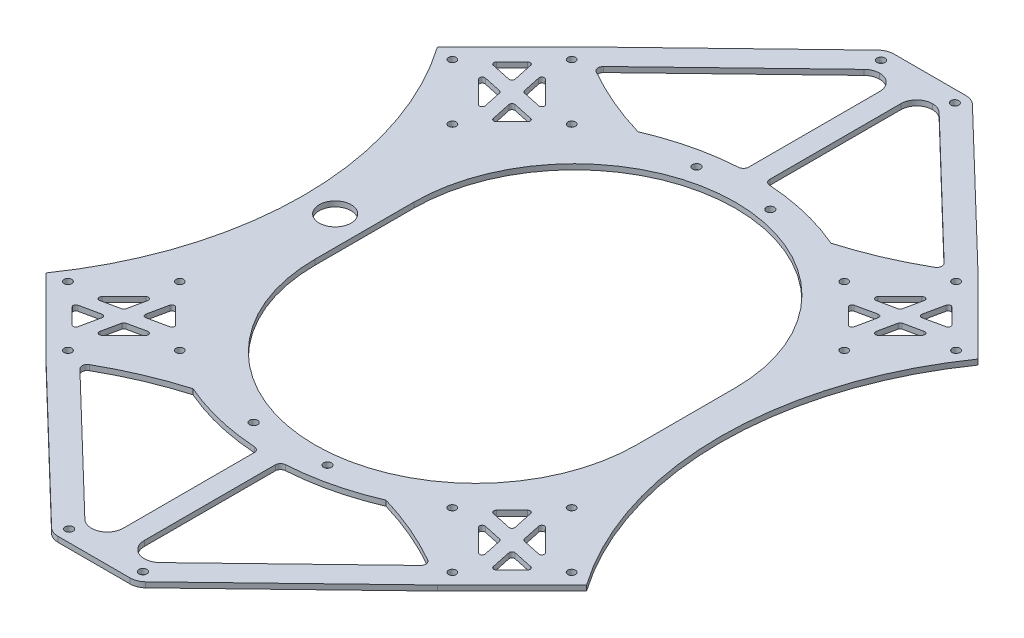
SolidWorks part; units mm, degrees
material "Thornel Mat VMA"
ref_plane "前视基准面" through (0, 0, 0) normal (0, 0, 1) x (1, 0, 0)
ref_plane "上视基准面" through (0, 0, 0) normal (0, 1, 0) x (1, 0, 0)
ref_plane "右视基准面" through (0, 0, 0) normal (1, 0, 0) x (0, 0, -1)
sketch "草图1" plane through (0, 0, 0) normal (0, 1, 0) x (1, 0, 0)
  line L0 (-74.2462, 102.5305) -> (-102.5305, 74.2462)
  line L1 (74.2462, 102.5305) -> (-74.2462, 102.5305)
  line L2 (102.5305, 74.2462) -> (102.5305, -74.2462)
  line L3 (74.2462, -102.5305) -> (-74.2462, -102.5305)
  line L4 (-102.5305, 74.2462) -> (-102.5305, -74.2462)
  line L5 (102.5305, 102.5305) -> (-102.5305, -102.5305) construction
  line L6 (102.5305, -102.5305) -> (-102.5305, 102.5305) construction
  line L7 (102.5305, -74.2462) -> (74.2462, -102.5305)
  line L8 (-102.5305, -74.2462) -> (-74.2462, -102.5305)
  line L9 (74.2462, 102.5305) -> (102.5305, 74.2462)
  line L10 (-102.5305, 102.5305) -> (-102.5305, -102.5305) construction
  line L11 (-102.5305, -102.5305) -> (102.5305, -102.5305) construction
  line L12 (102.5305, -102.5305) -> (102.5305, 102.5305) construction
  line L13 (102.5305, 102.5305) -> (-102.5305, 102.5305) construction
  point P0 (0, 0)
  dimension "D1" = 250
  dimension "D2" = 40
extrude "凸台-拉伸1" add sketch "草图1" along normal blind 2
hole_wizard "孔1" positions "草图4" profile "草图5" legacy
sketch "草图4" plane through (0, 2, 0) normal (0, 1, 0) x (1, 0, 0)
  point P0 (-95.5397, 72.9159)
  point P3 (-74.3265, 51.7027)
  point P6 (-51.6991, 74.3301)
  point P9 (-72.9123, 95.5433)
  point P16 (72.9159, 95.5397)
  point P17 (51.7027, 74.3265)
  point P18 (74.3301, 51.6991)
  point P19 (95.5433, 72.9123)
  point P20 (95.5397, -72.9159)
  point P21 (74.3265, -51.7027)
  point P22 (51.6991, -74.3301)
  point P23 (72.9123, -95.5433)
  point P24 (-72.9159, -95.5397)
  point P25 (-51.7027, -74.3265)
  point P26 (-74.3301, -51.6991)
  point P27 (-95.5433, -72.9123)
  dimension "D1" = 4
sketch "草图5" plane through (-95.5397, 2, -72.9159) normal (1, 0, 0) x (0, 0, 1)
  line L0 (0, 0) -> (0, 100)
  line L1 (0, 100) -> (1.45, 100)
  line L2 (1.45, 100) -> (1.45, 0)
  line L3 (1.45, 0) -> (0, 0)
  line L4 (0, 110) -> (0, -10) construction
  dimension "直径" = 2.9
  dimension "深度" = 100
sketch "草图7" plane through (0, 2, 0) normal (0, 1, 0) x (1, 0, 0)
  line L0 (-95.5397, 72.9159) -> (-51.6991, 74.3301) construction
  line L1 (-86.393, 80.4842) -> (-80.4806, 86.3966)
  line L2 (-84.1601, 71.4358) -> (-75.8066, 63.0823)
  line L3 (-71.4322, 84.1637) -> (-63.0787, 75.8102)
  line L4 (-66.7582, 60.8494) -> (-60.8458, 66.7618)
  line L5 (-89.8008, 77.0764) -> (-57.438, 70.1696) construction
  line L6 (-77.0728, 89.8044) -> (-70.166, 57.4416) construction
  line L7 (-49.2242, 67.6126) -> (-79.6109, 97.9993) construction
  line L8 (-74.2462, 102.5305) -> (-102.5305, 74.2462) construction
  line L9 (-85.8946, 78.7991) -> (-78.378, 77.1949)
  line L10 (-83.2443, 73.1208) -> (-76.36, 71.6516)
  line L11 (-87.6941, 79.1831) -> (-89.8008, 77.0764) construction
  line L12 (-89.8008, 77.0764) -> (-86.5509, 73.8265) construction
  line L13 (-60.6879, 73.4195) -> (-57.438, 70.1696) construction
  line L14 (-57.438, 70.1696) -> (-59.5447, 68.0629) construction
  line L15 (-67.4604, 74.8648) -> (-68.504, 69.975) construction
  line L16 (-73.6194, 73.623) -> (-67.2554, 79.987) construction
  line L17 (-74.1216, 63.9981) -> (-75.5908, 70.8824)
  line L18 (-68.4433, 61.3478) -> (-70.0475, 68.8644)
  line L19 (-70.8788, 75.5944) -> (-63.9945, 74.1252)
  line L20 (-77.1913, 78.3816) -> (-78.7955, 85.8982)
  line L21 (-68.8608, 70.0511) -> (-61.3442, 68.4469)
  line L22 (-71.648, 76.3636) -> (-73.1172, 83.2479)
  line L23 (80.4842, 86.393) -> (86.3966, 80.4806)
  line L24 (71.4358, 84.1601) -> (63.0823, 75.8066)
  line L25 (84.1637, 71.4322) -> (75.8102, 63.0787)
  line L26 (60.8494, 66.7582) -> (66.7618, 60.8458)
  line L27 (78.7991, 85.8946) -> (77.1949, 78.378)
  line L28 (73.1208, 83.2443) -> (71.6516, 76.36)
  line L29 (63.9981, 74.1216) -> (70.8824, 75.5908)
  line L30 (61.3478, 68.4433) -> (68.8644, 70.0475)
  line L31 (75.5944, 70.8788) -> (74.1252, 63.9945)
  line L32 (78.3816, 77.1913) -> (85.8982, 78.7955)
  line L33 (70.0511, 68.8608) -> (68.4469, 61.3442)
  line L34 (76.3636, 71.648) -> (83.2479, 73.1172)
  line L35 (72.9159, 95.5397) -> (74.3301, 51.6991) construction
  line L36 (77.0764, 89.8008) -> (70.1696, 57.438) construction
  line L37 (89.8044, 77.0728) -> (57.4416, 70.166) construction
  line L38 (79.1831, 87.6941) -> (77.0764, 89.8008) construction
  line L39 (77.0764, 89.8008) -> (73.8265, 86.5509) construction
  line L40 (73.4195, 60.6879) -> (70.1696, 57.438) construction
  line L41 (70.1696, 57.438) -> (68.0629, 59.5447) construction
  line L42 (74.8648, 67.4604) -> (69.975, 68.504) construction
  line L43 (73.623, 73.6194) -> (79.987, 67.2554) construction
  line L44 (86.393, -80.4842) -> (80.4806, -86.3966)
  line L45 (84.1601, -71.4358) -> (75.8066, -63.0823)
  line L46 (71.4322, -84.1637) -> (63.0787, -75.8102)
  line L47 (66.7582, -60.8494) -> (60.8458, -66.7618)
  line L48 (85.8946, -78.7991) -> (78.378, -77.1949)
  line L49 (83.2443, -73.1208) -> (76.36, -71.6516)
  line L50 (74.1216, -63.9981) -> (75.5908, -70.8824)
  line L51 (68.4433, -61.3478) -> (70.0475, -68.8644)
  line L52 (70.8788, -75.5944) -> (63.9945, -74.1252)
  line L53 (77.1913, -78.3816) -> (78.7955, -85.8982)
  line L54 (68.8608, -70.0511) -> (61.3442, -68.4469)
  line L55 (71.648, -76.3636) -> (73.1172, -83.2479)
  line L56 (95.5397, -72.9159) -> (51.6991, -74.3301) construction
  line L57 (89.8008, -77.0764) -> (57.438, -70.1696) construction
  line L58 (77.0728, -89.8044) -> (70.166, -57.4416) construction
  line L59 (87.6941, -79.1831) -> (89.8008, -77.0764) construction
  line L60 (89.8008, -77.0764) -> (86.5509, -73.8265) construction
  line L61 (60.6879, -73.4195) -> (57.438, -70.1696) construction
  line L62 (57.438, -70.1696) -> (59.5447, -68.0629) construction
  line L63 (67.4604, -74.8648) -> (68.504, -69.975) construction
  line L64 (73.6194, -73.623) -> (67.2554, -79.987) construction
  line L65 (-80.4842, -86.393) -> (-86.3966, -80.4806)
  line L66 (-71.4358, -84.1601) -> (-63.0823, -75.8066)
  line L67 (-84.1637, -71.4322) -> (-75.8102, -63.0787)
  line L68 (-60.8494, -66.7582) -> (-66.7618, -60.8458)
  line L69 (-78.7991, -85.8946) -> (-77.1949, -78.378)
  line L70 (-73.1208, -83.2443) -> (-71.6516, -76.36)
  line L71 (-63.9981, -74.1216) -> (-70.8824, -75.5908)
  line L72 (-61.3478, -68.4433) -> (-68.8644, -70.0475)
  line L73 (-75.5944, -70.8788) -> (-74.1252, -63.9945)
  line L74 (-78.3816, -77.1913) -> (-85.8982, -78.7955)
  line L75 (-70.0511, -68.8608) -> (-68.4469, -61.3442)
  line L76 (-76.3636, -71.648) -> (-83.2479, -73.1172)
  line L77 (-72.9159, -95.5397) -> (-74.3301, -51.6991) construction
  line L78 (-77.0764, -89.8008) -> (-70.1696, -57.438) construction
  line L79 (-89.8044, -77.0728) -> (-57.4416, -70.166) construction
  line L80 (-79.1831, -87.6941) -> (-77.0764, -89.8008) construction
  line L81 (-77.0764, -89.8008) -> (-73.8265, -86.5509) construction
  line L82 (-73.4195, -60.6879) -> (-70.1696, -57.438) construction
  line L83 (-70.1696, -57.438) -> (-68.0629, -59.5447) construction
  line L84 (-74.8648, -67.4604) -> (-69.975, -68.504) construction
  line L85 (-73.623, -73.6194) -> (-79.987, -67.2554) construction
  arc A0 (-63.0787, 75.8102) -> (-63.9945, 74.1252) centre (-63.7858, 75.1031) cw
  arc A1 (-70.8788, 75.5944) -> (-71.648, 76.3636) centre (-70.67, 76.5724) cw
  arc A2 (-71.4322, 84.1637) -> (-73.1172, 83.2479) centre (-72.1393, 83.4566) ccw
  arc A3 (-78.7955, 85.8982) -> (-80.4806, 86.3966) centre (-79.7735, 85.6895) ccw
  arc A4 (-85.8946, 78.7991) -> (-86.393, 80.4842) centre (-85.6859, 79.7771) cw
  arc A5 (-78.378, 77.1949) -> (-77.1913, 78.3816) centre (-78.1693, 78.1729) ccw
  arc A6 (-66.7582, 60.8494) -> (-68.4433, 61.3478) centre (-67.4653, 61.5565) cw
  arc A7 (-60.8458, 66.7618) -> (-61.3442, 68.4469) centre (-61.5529, 67.4689) ccw
  arc A8 (-68.8608, 70.0511) -> (-70.0475, 68.8644) centre (-69.0695, 69.0731) ccw
  arc A9 (-75.8066, 63.0823) -> (-74.1216, 63.9981) centre (-75.0995, 63.7894) ccw
  arc A10 (-75.5908, 70.8824) -> (-76.36, 71.6516) centre (-76.5688, 70.6736) ccw
  arc A11 (-83.2443, 73.1208) -> (-84.1601, 71.4358) centre (-83.453, 72.1429) ccw
  arc A12 (75.8102, 63.0787) -> (74.1252, 63.9945) centre (75.1031, 63.7858) cw
  arc A13 (75.5944, 70.8788) -> (76.3636, 71.648) centre (76.5724, 70.67) cw
  arc A14 (84.1637, 71.4322) -> (83.2479, 73.1172) centre (83.4566, 72.1393) ccw
  arc A15 (85.8982, 78.7955) -> (86.3966, 80.4806) centre (85.6895, 79.7735) ccw
  arc A16 (78.7991, 85.8946) -> (80.4842, 86.393) centre (79.7771, 85.6859) cw
  arc A17 (77.1949, 78.378) -> (78.3816, 77.1913) centre (78.1729, 78.1693) ccw
  arc A18 (60.8494, 66.7582) -> (61.3478, 68.4433) centre (61.5565, 67.4653) cw
  arc A19 (66.7618, 60.8458) -> (68.4469, 61.3442) centre (67.4689, 61.5529) ccw
  arc A20 (70.0511, 68.8608) -> (68.8644, 70.0475) centre (69.0731, 69.0695) ccw
  arc A21 (63.0823, 75.8066) -> (63.9981, 74.1216) centre (63.7894, 75.0995) ccw
  arc A22 (70.8824, 75.5908) -> (71.6516, 76.36) centre (70.6736, 76.5688) ccw
  arc A23 (73.1208, 83.2443) -> (71.4358, 84.1601) centre (72.1429, 83.453) ccw
  arc A24 (63.0787, -75.8102) -> (63.9945, -74.1252) centre (63.7858, -75.1031) cw
  arc A25 (70.8788, -75.5944) -> (71.648, -76.3636) centre (70.67, -76.5724) cw
  arc A26 (71.4322, -84.1637) -> (73.1172, -83.2479) centre (72.1393, -83.4566) ccw
  arc A27 (78.7955, -85.8982) -> (80.4806, -86.3966) centre (79.7735, -85.6895) ccw
  arc A28 (85.8946, -78.7991) -> (86.393, -80.4842) centre (85.6859, -79.7771) cw
  arc A29 (78.378, -77.1949) -> (77.1913, -78.3816) centre (78.1693, -78.1729) ccw
  arc A30 (66.7582, -60.8494) -> (68.4433, -61.3478) centre (67.4653, -61.5565) cw
  arc A31 (60.8458, -66.7618) -> (61.3442, -68.4469) centre (61.5529, -67.4689) ccw
  arc A32 (68.8608, -70.0511) -> (70.0475, -68.8644) centre (69.0695, -69.0731) ccw
  arc A33 (75.8066, -63.0823) -> (74.1216, -63.9981) centre (75.0995, -63.7894) ccw
  arc A34 (75.5908, -70.8824) -> (76.36, -71.6516) centre (76.5688, -70.6736) ccw
  arc A35 (83.2443, -73.1208) -> (84.1601, -71.4358) centre (83.453, -72.1429) ccw
  arc A36 (-75.8102, -63.0787) -> (-74.1252, -63.9945) centre (-75.1031, -63.7858) cw
  arc A37 (-75.5944, -70.8788) -> (-76.3636, -71.648) centre (-76.5724, -70.67) cw
  arc A38 (-84.1637, -71.4322) -> (-83.2479, -73.1172) centre (-83.4566, -72.1393) ccw
  arc A39 (-85.8982, -78.7955) -> (-86.3966, -80.4806) centre (-85.6895, -79.7735) ccw
  arc A40 (-78.7991, -85.8946) -> (-80.4842, -86.393) centre (-79.7771, -85.6859) cw
  arc A41 (-77.1949, -78.378) -> (-78.3816, -77.1913) centre (-78.1729, -78.1693) ccw
  arc A42 (-60.8494, -66.7582) -> (-61.3478, -68.4433) centre (-61.5565, -67.4653) cw
  arc A43 (-66.7618, -60.8458) -> (-68.4469, -61.3442) centre (-67.4689, -61.5529) ccw
  arc A44 (-70.0511, -68.8608) -> (-68.8644, -70.0475) centre (-69.0731, -69.0695) ccw
  arc A45 (-63.0823, -75.8066) -> (-63.9981, -74.1216) centre (-63.7894, -75.0995) ccw
  arc A46 (-70.8824, -75.5908) -> (-71.6516, -76.36) centre (-70.6736, -76.5688) ccw
  arc A47 (-73.1208, -83.2443) -> (-71.4358, -84.1601) centre (-72.1429, -83.453) ccw
  point P5 (-73.6194, 73.623)
  point P14 (-72.9123, 95.5433)
  point P21 (-67.9822, 72.4199)
  point P38 (-71.5127, 75.7297)
  point P41 (-73.8229, 86.5545)
  point P44 (-79.1795, 87.6977)
  point P50 (-76.8693, 76.8729)
  point P53 (-68.0593, 59.5483)
  point P59 (-70.3695, 70.3731)
  point P62 (-73.4159, 60.6915)
  point P73 (73.623, 73.6194)
  point P84 (72.4199, 67.9822)
  point P126 (73.6194, -73.623)
  point P137 (67.9822, -72.4199)
  point P179 (-73.623, -73.6194)
  point P190 (-72.4199, -67.9822)
  point P230 (0, 0)
  dimension "D4" = 1
  dimension "D1" = 7
  dimension "D2" = 7
  dimension "D3" = 5
  dimension "D5" = 4
extrude "切除-拉伸2" cut sketch "草图7" against normal through all both and the other way through all
sketch "草图8" plane through (0, 2, 0) normal (0, 1, 0) x (1, 0, 0)
  line L0 (-208.5651, 0) -> (0, 0) construction
  line L1 (-102.5305, -74.2462) -> (-50.5427, 0) construction
  line L3 (0, 0) -> (-88.3883, -88.3883) construction
  line L4 (-102.5305, -74.2462) -> (-74.2462, -102.5305) construction
  line L5 (0, 102.5305) -> (0, -102.5305) construction
  line L6 (74.2462, 102.5305) -> (-74.2462, 102.5305) construction
  line L7 (-74.2462, -102.5305) -> (74.2462, -102.5305) construction
  circle A0 centre (-208.5651, 0) radius 129.4443
  circle A2 centre (0, 208.5651) radius 129.4443
  circle A3 centre (208.5651, 0) radius 129.4443
  circle A4 centre (0, -208.5651) radius 129.4443
  point P28 (0, 0)
  dimension "D1" = 10
  dimension "D2" = 4
extrude "切除-拉伸3" cut sketch "草图8" against normal through all both and the other way through all
sketch "草图9" plane through (0, 2, 0) normal (0, 1, 0) x (1, 0, 0)
  line L0 (0, 0) -> (-79.1207, 0) construction
  arc A0 (-102.5305, -74.2462) -> (-102.5305, 74.2462) centre (-208.5651, 0) ccw construction
  circle A1 centre (-67.0707, 0) radius 6.05
  point P8 (-73.1207, 0)
  dimension "D1" = 12.1
  dimension "D2" = 6
extrude "切除-拉伸4" cut sketch "草图9" against normal through all both and the other way through all
sketch "草图11" plane through (0, 2, 0) normal (0, 1, 0) x (1, 0, 0)
  line L0 (5.9793, 0) -> (0, 0) construction
  line L1 (-61.0207, 0) -> (-54.0207, 0) construction
  circle A0 centre (5.9793, 0) radius 60
  circle A1 centre (-67.0707, 0) radius 6.05 construction
  point P3 (-54.0207, 0)
  point P7 (-61.0207, 0)
  dimension "D1" = 120
  dimension "D2" = 7
extrude "切除-拉伸6" cut sketch "草图11" against normal through all both and the other way through all
sketch "草图12" plane through (0, 2, 0) normal (0, 1, 0) x (1, 0, 0)
  line L0 (-74.2462, 102.5305) -> (-17.8384, 156.8229)
  line L1 (-13.6776, 158.5) -> (13.6776, 158.5)
  line L2 (17.8384, 156.8229) -> (74.2462, 102.5305)
  line L3 (0, 158.5) -> (0, 0) construction
  line L4 (-74.2462, 102.5305) -> (-66.3304, 96.7253)
  line L5 (-64.5868, 99.3361) -> (-14.2108, 147.8229)
  line L6 (-10.05, 149.5) -> (-10, 149.5)
  line L7 (14.2108, 147.8229) -> (64.5868, 99.3361)
  line L8 (67.6574, 95.9526) -> (74.2462, 102.5305)
  line L9 (-4, 143.5) -> (-4, 81.2621)
  line L10 (-11.198, 64.0438) -> (11.198, 64.0438)
  line L11 (4, 81.2621) -> (4, 143.5)
  line L12 (10, 149.5) -> (10.05, 149.5)
  line L13 (-40.9809, 134.5483) -> (-34.7397, 128.0639) construction
  line L14 (-4, 149.5) -> (-4, 158.5) construction
  line L15 (-66.3304, 96.7253) -> (-11.198, 64.0438)
  line L16 (11.198, 64.0438) -> (67.6574, 95.9526)
  line L17 (-4, 79.1826) -> (4, 79.1826) construction
  line L18 (-79.1207, 0) -> (79.1207, 0) construction
  line L19 (-4, -79.1826) -> (4, -79.1826) construction
  line L20 (-4, -149.5) -> (-4, -158.5) construction
  line L21 (-40.9809, -134.5483) -> (-34.7397, -128.0639) construction
  line L22 (11.198, -64.0438) -> (67.6574, -95.9526)
  line L23 (-66.3304, -96.7253) -> (-11.198, -64.0438)
  line L24 (10, -149.5) -> (10.05, -149.5)
  line L25 (4, -81.2621) -> (4, -143.5)
  line L26 (-11.198, -64.0438) -> (11.198, -64.0438)
  line L27 (-4, -143.5) -> (-4, -81.2621)
  line L28 (67.6574, -95.9526) -> (74.2462, -102.5305)
  line L29 (14.2108, -147.8229) -> (64.5868, -99.3361)
  line L30 (-10.05, -149.5) -> (-10, -149.5)
  line L31 (-64.5868, -99.3361) -> (-14.2108, -147.8229)
  line L32 (-74.2462, -102.5305) -> (-66.3304, -96.7253)
  line L33 (17.8384, -156.8229) -> (74.2462, -102.5305)
  line L34 (-13.6776, -158.5) -> (13.6776, -158.5)
  line L35 (-74.2462, -102.5305) -> (-17.8384, -156.8229)
  arc A0 (-64.1917, 96.1584) -> (-6.0942, 79.2643) centre (0, 208.5651) ccw
  arc A1 (-74.2462, 102.5305) -> (74.2462, 102.5305) centre (0, 208.5651) ccw construction
  arc A2 (6.0942, 79.2643) -> (64.1917, 96.1584) centre (0, 208.5651) ccw
  arc A3 (-102.5305, -74.2462) -> (-102.5305, 74.2462) centre (-208.5651, 0) ccw construction
  arc A4 (102.5305, 74.2462) -> (102.5305, -74.2462) centre (208.5651, 0) ccw construction
  arc A5 (64.1917, 96.1584) -> (64.5868, 99.3361) centre (63.1999, 97.8951) ccw
  arc A6 (-64.5868, 99.3361) -> (-64.1917, 96.1584) centre (-63.1999, 97.8951) ccw
  arc A7 (6.0942, 79.2643) -> (4, 81.2621) centre (6, 81.2621) cw
  arc A8 (-4, 81.2621) -> (-6.0942, 79.2643) centre (-6, 81.2621) cw
  arc A9 (17.8384, 156.8229) -> (13.6776, 158.5) centre (13.6776, 152.5) ccw
  arc A10 (-13.6776, 158.5) -> (-17.8384, 156.8229) centre (-13.6776, 152.5) ccw
  arc A11 (-10.05, 149.5) -> (-14.2108, 147.8229) centre (-10.05, 143.5) ccw
  arc A12 (14.2108, 147.8229) -> (10.05, 149.5) centre (10.05, 143.5) ccw
  arc A13 (4, 143.5) -> (10, 149.5) centre (10, 143.5) cw
  arc A14 (-4, 143.5) -> (-10, 149.5) centre (-10, 143.5) ccw
  arc A15 (-4, -143.5) -> (-10, -149.5) centre (-10, -143.5) cw
  arc A16 (4, -143.5) -> (10, -149.5) centre (10, -143.5) ccw
  arc A17 (14.2108, -147.8229) -> (10.05, -149.5) centre (10.05, -143.5) cw
  arc A18 (-10.05, -149.5) -> (-14.2108, -147.8229) centre (-10.05, -143.5) cw
  arc A19 (-13.6776, -158.5) -> (-17.8384, -156.8229) centre (-13.6776, -152.5) cw
  arc A20 (17.8384, -156.8229) -> (13.6776, -158.5) centre (13.6776, -152.5) cw
  arc A21 (-4, -81.2621) -> (-6.0942, -79.2643) centre (-6, -81.2621) ccw
  arc A22 (6.0942, -79.2643) -> (4, -81.2621) centre (6, -81.2621) ccw
  arc A23 (-64.5868, -99.3361) -> (-64.1917, -96.1584) centre (-63.1999, -97.8951) cw
  arc A24 (64.1917, -96.1584) -> (64.5868, -99.3361) centre (63.1999, -97.8951) cw
  arc A25 (6.0942, -79.2643) -> (64.1917, -96.1584) centre (0, -208.5651) cw
  arc A26 (-64.1917, -96.1584) -> (-6.0942, -79.2643) centre (0, -208.5651) cw
  point P17 (0, 64.0438)
  point P24 (0, 79.1826)
  point P40 (66.4912, 97.5031)
  point P43 (-66.4912, 97.5031)
  point P60 (4, 149.5)
  point P107 (4, -149.5)
  point P108 (-66.4912, -97.5031)
  point P109 (66.4912, -97.5031)
  point P110 (0, -79.1826)
  point P111 (0, -64.0438)
  point P112 (0, 0)
  dimension "D4" = 2
  dimension "D5" = 2
  dimension "D6" = 6
  dimension "D1" = 158.5
  dimension "D2" = 9
  dimension "D3" = 8
  dimension "D7" = 0.05
extrude "凸台-拉伸2" add sketch "草图12" against normal up to surface (2 mm away) up to face at (5.9793, 0, 60)
sketch "草图14" plane through (0, 2, 0) normal (0, 1, 0) x (1, 0, 0)
  line L0 (0, 132.5) -> (0, 0) construction
  line L1 (10, 111) -> (-10, 111)
  line L2 (10, 111) -> (10, 154)
  line L3 (10, 154) -> (-10, 154)
  line L4 (-10, 111) -> (-10, 154)
  line L5 (10, 111) -> (-10, 154) construction
  line L6 (10, 154) -> (-10, 111) construction
  line L7 (-10, 154) -> (-13.6309, 154) construction
  line L8 (-13.6309, 158.5) -> (-13.6309, 149.5) construction
  line L9 (13.6776, 158.5) -> (-13.6776, 158.5) construction
  line L10 (-10, 149.5) -> (-10.05, 149.5) construction
  line L11 (-79.1207, 0) -> (79.1207, 0) construction
  line L12 (-13.6309, -158.5) -> (-13.6309, -149.5) construction
  line L13 (-10, -154) -> (-13.6309, -154) construction
  line L14 (10, -154) -> (-10, -111) construction
  line L15 (10, -111) -> (-10, -154) construction
  line L16 (-10, -111) -> (-10, -154)
  line L17 (10, -154) -> (-10, -154)
  line L18 (10, -111) -> (10, -154)
  line L19 (10, -111) -> (-10, -111)
  arc A0 (-102.5305, -74.2462) -> (-102.5305, 74.2462) centre (-208.5651, 0) ccw construction
  arc A1 (102.5305, 74.2462) -> (102.5305, -74.2462) centre (208.5651, 0) ccw construction
  point P0 (0, 132.5)
  point P30 (0, -132.5)
  dimension "D1" = 20
  dimension "D2" = 43
sketch "草图15" plane through (0, 2, 0) normal (0, 1, 0) x (1, 0, 0)
  line L0 (-4, 81.2621) -> (-4, 143.5) construction
  line L1 (-40.3412, 82.6837) -> (-31.9185, 62.6852)
  line L2 (44.6358, 80.4465) -> (36.2732, 60.2701)
  line L3 (-42.4295, -81.6317) -> (-34.5316, -61.2845)
  line L4 (41.391, -82.1632) -> (34.5498, -61.2743)
  line L5 (-4, 105.5527) -> (4, 105.5527)
  line L6 (-4, 105.5527) -> (-4, 93.8083)
  line L7 (-4, -143.5) -> (-4, -81.2621) construction
  line L8 (4, 105.5527) -> (4, 93.8083)
  line L10 (-4, -107.2373) -> (4, -107.2373)
  line L11 (-4, -107.2373) -> (-4, -93.8083)
  line L13 (4, -107.2373) -> (4, -93.8083)
  arc A0 (-42.4295, -81.6317) -> (-5.8723, -91.8124) centre (0, 0) ccw
  arc A1 (-5.8723, 91.8124) -> (-40.3412, 82.6837) centre (0, 0) ccw
  arc A2 (-34.5316, -61.2845) -> (34.5498, -61.2743) centre (0, 0) ccw
  arc A3 (36.2732, 60.2701) -> (-31.9185, 62.6852) centre (0, 0) ccw
  arc A4 (44.6358, 80.4465) -> (5.8723, 91.8124) centre (0, 0) ccw
  arc A5 (5.8723, 91.8124) -> (4, 93.8083) centre (6, 93.8083) cw
  arc A6 (-5.8723, 91.8124) -> (-4, 93.8083) centre (-6, 93.8083) ccw
  arc A7 (5.8723, -91.8124) -> (41.391, -82.1632) centre (0, 0) ccw
  arc A8 (5.8723, -91.8124) -> (4, -93.8083) centre (6, -93.8083) ccw
  arc A9 (-4, -93.8083) -> (-5.8723, -91.8124) centre (-6, -93.8083) ccw
  point P20 (-4, 91.913)
  dimension "D1" = 92
  dimension "D2" = 2
  dimension "D3" = 2
extrude "凸台-拉伸3" add sketch "草图15" against normal up to surface (2 mm away) up to face at (0, 0, 0)
hole_wizard "孔2" positions "草图16" profile "草图17" legacy
sketch "草图16" plane through (0, 2, 0) normal (0, 1, 0) x (1, 0, 0)
  line L0 (-14, 154) -> (14, 154) construction
  line L3 (-14, -154) -> (14, -154) construction
  line L5 (0, -154) -> (0, 154) construction
  line L7 (10, 154) -> (-10, 154) construction
  line L8 (10, -154) -> (-10, -154) construction
  line L9 (-14, -84) -> (14, -84) construction
  line L10 (0, -84) -> (0, 224) construction
  line L11 (-14, 84) -> (14, 84) construction
  point P0 (-14, 154)
  point P3 (14, 154)
  point P12 (-14, -154)
  point P15 (14, -154)
  point P54 (-14, -84)
  point P55 (14, -84)
  point P64 (-14, 84)
  point P65 (14, 84)
  dimension "D1" = 28
  dimension "D2" = 28
  dimension "D5" = 168
  dimension "D3" = 2
  dimension "D4" = 2
sketch "草图17" plane through (-14, 2, -154) normal (1, 0, 0) x (0, 0, 1)
  line L0 (0, 0) -> (0, 100)
  line L1 (0, 100) -> (1.5, 100)
  line L2 (1.5, 100) -> (1.5, 0)
  line L3 (1.5, 0) -> (0, 0)
  line L4 (0, 110) -> (0, -10) construction
  dimension "直径" = 3
  dimension "深度" = 100
sketch "草图18" plane through (0, 2, 0) normal (0, 1, 0) x (1, 0, 0)
  line L0 (-56.0207, 0) -> (4.9793, 0) construction
  line L1 (4.9793, 18.75) -> (4.9793, -18.75) construction
  line L2 (65.9793, 18.75) -> (65.9793, -18.75)
  line L3 (-56.0207, 18.75) -> (-56.0207, -18.75)
  arc A1 (65.9793, 18.75) -> (-56.0207, 18.75) centre (4.9793, 18.75) ccw
  arc A2 (-56.0207, -18.75) -> (65.9793, -18.75) centre (4.9793, -18.75) ccw
  circle A3 centre (5.9793, 0) radius 60 construction
  point P0 (-56.0207, 0)
  point P1 (-54.0207, 0)
  point P5 (5.9793, 0)
  point P8 (4.9793, 0)
  dimension "D1" = 61
  dimension "D2" = 2
  dimension "D3" = 37.5
extrude "切除-拉伸7" cut sketch "草图18" against normal through all both and the other way through all
